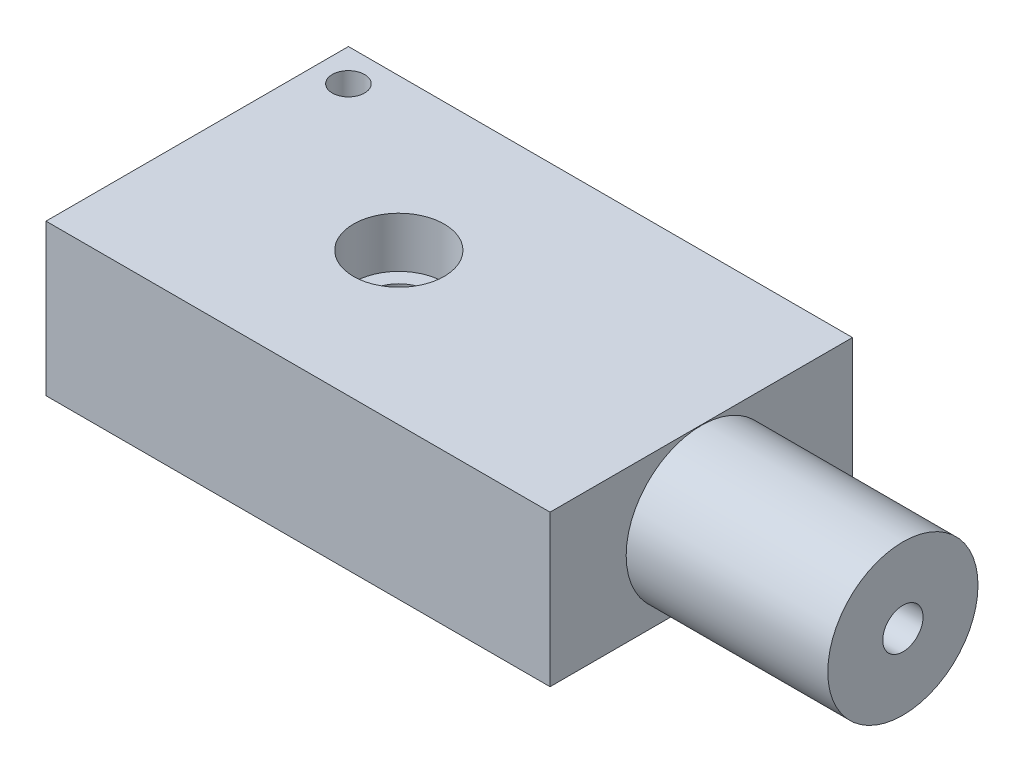
SolidWorks part; units mm, degrees
ref_plane "Front Plane" through (0, 0, 0) normal (0, 0, 1) x (1, 0, 0)
ref_plane "Top Plane" through (0, 0, 0) normal (0, 1, 0) x (1, 0, 0)
ref_plane "Right Plane" through (0, 0, 0) normal (1, 0, 0) x (0, 0, -1)
sketch "Sketch1" plane through (0, 0, 0) normal (0, 1, 0) x (1, 0, 0)
  line L1 (-21.9652, -12.534) -> (3.0348, -12.534)
  line L2 (-21.9652, -12.534) -> (-21.9652, 2.466)
  line L3 (-21.9652, 2.466) -> (3.0348, 2.466)
  line L4 (3.0348, -12.534) -> (3.0348, 2.466)
  dimension "D1" = 25
  dimension "D2" = 15
extrude "Boss-Extrude1" add sketch "Sketch1" along normal blind 7.5
sketch "Sketch2" plane through (3.0348, 0, 0) normal (1, 0, 0) x (0, 0, -1)
  line L0 (2.466, 7.5) -> (2.466, 0) construction
  line L1 (-12.534, 7.5) -> (2.466, 7.5) construction
  circle A0 centre (-5.034, 3.75) radius 3.725
  dimension "D1" = 7.45
  dimension "D2" = 7.5
  dimension "D3" = 3.75
extrude "Boss-Extrude2" add sketch "Sketch2" along normal blind 10
sketch "Sketch3" plane through (13.0348, 0, 0) normal (1, 0, 0) x (0, 0, -1)
  circle A0 centre (-5.034, 3.75) radius 1
  circle A1 centre (-5.034, 3.75) radius 3.725 construction
  dimension "D1" = 2
  dimension "D2" = 0
extrude "Cut-Extrude1" cut sketch "Sketch3" against normal blind 3
sketch "Sketch4" plane through (-21.9652, 0, 0) normal (-1, 0, 0) x (0, 0, 1)
  line L0 (-2.466, 7.5) -> (-2.466, 0) construction
  line L1 (-2.466, 5.75) -> (7.534, 5.75)
  line L2 (-2.466, 5.75) -> (-2.466, 1.75)
  line L3 (-2.466, 1.75) -> (7.534, 1.75)
  line L4 (7.534, 5.75) -> (7.534, 1.75)
  line L5 (12.534, 7.5) -> (12.534, 0) construction
  line L6 (-2.466, 7.5) -> (12.534, 7.5) construction
  dimension "D1" = 0
  dimension "D2" = 5
  dimension "D3" = 4
  dimension "D4" = 1.75
extrude "Cut-Extrude2" cut sketch "Sketch4" against normal blind 5
sketch "Sketch5" plane through (0, 7.5, 0) normal (0, 1, 0) x (1, 0, 0)
  line L1 (-21.9652, 2.466) -> (-21.9652, -12.534) construction
  line L2 (3.0348, 2.466) -> (-21.9652, 2.466) construction
  circle A0 centre (-20.3652, 0.866) radius 0.8
  dimension "D1" = 1.6
  dimension "D2" = 1.6
  dimension "D3" = 1.6
extrude "Cut-Extrude3" cut sketch "Sketch5" against normal blind 7.5
sketch "Sketch6" plane through (0, 7.5, 0) normal (0, 1, 0) x (1, 0, 0)
  line L0 (3.0348, 2.466) -> (-21.9652, 2.466) construction
  line L1 (-21.9652, 2.466) -> (-21.9652, -12.534) construction
  circle A0 centre (-11.9652, -5.034) radius 2.25
  circle A1 centre (-11.9652, -5.034) radius 1.5
  dimension "D1" = 3
  dimension "D2" = 4.5
  dimension "D3" = 7.5
  dimension "D4" = 10
extrude "Cut-Extrude4" cut sketch "Sketch6" against normal blind 7.5 contours A1 region at (-11.9652, 7.5, 5.034)
extrude "Cut-Extrude5" cut sketch "Sketch6<3>" against normal blind 2.5 contours A0 A1 region at (-14.1515, 7.5, 5.034)
sketch "Sketch6<3>" plane through (0, 7.5, 0) normal (0, 1, 0) x (1, 0, 0) same geometry as "Sketch6"
sketch "Sketch7" plane through (0, 0, 0) normal (0, -1, 0) x (1, 0, 0)
  circle A0 centre (-11.9652, 5.034) radius 2.25
  dimension "D1" = 4.5
extrude "Cut-Extrude6" cut sketch "Sketch7" against normal blind 2.5
